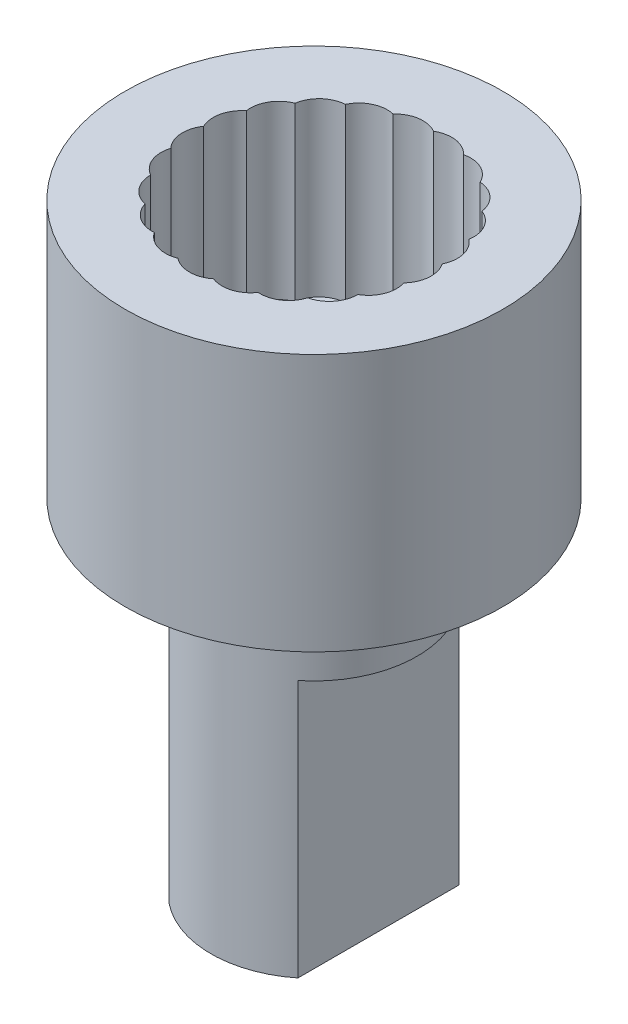
SolidWorks part; units mm, degrees
ref_plane "Front Plane" through (0, 0, 0) normal (0, 0, 1) x (1, 0, 0)
ref_plane "Top Plane" through (0, 0, 0) normal (0, 1, 0) x (1, 0, 0)
ref_plane "Right Plane" through (0, 0, 0) normal (1, 0, 0) x (0, 0, -1)
sketch "Sketch1" plane through (0, 0, 0) normal (0, 1, 0) x (1, 0, 0)
  line L0 (0, 0) -> (0, 4.4464) construction
  line L1 (0, 0) -> (0.6627, 4.3968) construction
  line L2 (0, 0) -> (1.3106, 4.2489) construction
  line L3 (0, 0) -> (1.9292, 4.0061) construction
  line L4 (0, 0) -> (2.5048, 3.6738) construction
  line L5 (0, 0) -> (3.0243, 3.2595) construction
  line L6 (0, 0) -> (3.4764, 2.7723) construction
  line L7 (0, 0) -> (3.8507, 2.2232) construction
  line L8 (0, 0) -> (4.1391, 1.6245) construction
  line L9 (0, 0) -> (4.3349, 0.9894) construction
  line L10 (0, 0) -> (4.434, 0.3323) construction
  line L11 (0, 0) -> (4.434, -0.3323) construction
  line L12 (0, 0) -> (4.3349, -0.9894) construction
  line L13 (0, 0) -> (4.1391, -1.6245) construction
  line L14 (0, 0) -> (3.8507, -2.2232) construction
  line L15 (0, 0) -> (3.4764, -2.7723) construction
  line L16 (0, 0) -> (3.0243, -3.2595) construction
  line L17 (0, 0) -> (2.5048, -3.6738) construction
  line L18 (0, 0) -> (1.9292, -4.0061) construction
  line L19 (0, 0) -> (1.3106, -4.2489) construction
  line L20 (0, 0) -> (0.6627, -4.3968) construction
  line L21 (0, 0) -> (0, -4.4464) construction
  line L22 (0, 0) -> (-0.6627, -4.3968) construction
  line L23 (0, 0) -> (-1.3106, -4.2489) construction
  line L24 (0, 0) -> (-1.9292, -4.0061) construction
  line L25 (0, 0) -> (-2.5048, -3.6738) construction
  line L26 (0, 0) -> (-3.0243, -3.2595) construction
  line L27 (0, 0) -> (-3.4764, -2.7723) construction
  line L28 (0, 0) -> (-3.8507, -2.2232) construction
  line L29 (0, 0) -> (-4.1391, -1.6245) construction
  line L30 (0, 0) -> (-4.3349, -0.9894) construction
  line L31 (0, 0) -> (-4.434, -0.3323) construction
  line L32 (0, 0) -> (-4.434, 0.3323) construction
  line L33 (0, 0) -> (-4.3349, 0.9894) construction
  line L34 (0, 0) -> (-4.1391, 1.6245) construction
  line L35 (0, 0) -> (-3.8507, 2.2232) construction
  line L36 (0, 0) -> (-3.4764, 2.7723) construction
  line L37 (0, 0) -> (-3.0243, 3.2595) construction
  line L38 (0, 0) -> (-2.5048, 3.6738) construction
  line L39 (0, 0) -> (-1.9292, 4.0061) construction
  line L40 (0, 0) -> (-1.3106, 4.2489) construction
  line L41 (0, 0) -> (-0.6627, 4.3968) construction
  circle A1 centre (0, 0) radius 2.45 construction
  circle A5 centre (0, 0) radius 3.95
  circle A14 centre (0, 0) radius 2.2653 construction
  arc A22 (-0.1666, 2.3451) -> (0, 2.2653) centre (0, 2.479) ccw
  arc A23 (-0.1666, 2.3451) -> (-0.532, 2.2901) centre (-0.3333, 2.2113) ccw
  arc A24 (-0.6677, 2.1646) -> (-0.532, 2.2901) centre (-0.7307, 2.3689) ccw
  arc A25 (0, 2.2653) -> (0.1666, 2.3451) centre (0, 2.479) ccw
  arc A26 (0.532, 2.2901) -> (0.1666, 2.3451) centre (0.3333, 2.2113) ccw
  arc A27 (0.532, 2.2901) -> (0.6677, 2.1646) centre (0.7307, 2.3689) ccw
  arc A28 (0.6677, 2.1646) -> (0.8505, 2.1918) centre (0.7307, 2.3689) ccw
  arc A29 (1.1834, 2.0315) -> (0.8505, 2.1918) centre (0.9703, 2.0148) ccw
  arc A30 (1.1834, 2.0315) -> (1.2761, 1.8716) centre (1.3965, 2.0483) ccw
  arc A31 (1.2761, 1.8716) -> (1.4588, 1.8438) centre (1.3965, 2.0483) ccw
  arc A32 (1.7296, 1.5925) -> (1.4588, 1.8438) centre (1.521, 1.6393) ccw
  arc A33 (1.7296, 1.5925) -> (1.7711, 1.4124) centre (1.9382, 1.5456) ccw
  arc A34 (1.7711, 1.4124) -> (1.9374, 1.3319) centre (1.9382, 1.5456) ccw
  arc A35 (2.1221, 1.0119) -> (1.9374, 1.3319) centre (1.9366, 1.1181) ccw
  arc A36 (2.1221, 1.0119) -> (2.1087, 0.8276) centre (2.3077, 0.9057) ccw
  arc A37 (2.1087, 0.8276) -> (2.2439, 0.7016) centre (2.3077, 0.9057) ccw
  arc A38 (2.3261, 0.3414) -> (2.2439, 0.7016) centre (2.1802, 0.4976) ccw
  arc A39 (2.3261, 0.3414) -> (2.2589, 0.1693) centre (2.4721, 0.1853) ccw
  arc A40 (2.2589, 0.1693) -> (2.351, 0.0091) centre (2.4721, 0.1853) ccw
  arc A41 (2.3234, -0.3594) -> (2.351, 0.0091) centre (2.23, -0.1671) ccw
  arc A42 (2.3234, -0.3594) -> (2.2085, -0.5041) centre (2.4169, -0.5516) ccw
  arc A43 (2.2085, -0.5041) -> (2.2493, -0.6843) centre (2.4169, -0.5516) ccw
  arc A44 (2.1143, -1.0283) -> (2.2493, -0.6843) centre (2.0817, -0.817) ccw
  arc A45 (2.1143, -1.0283) -> (1.9618, -1.1326) centre (2.1469, -1.2395) ccw
  arc A46 (1.9618, -1.1326) -> (1.9476, -1.3169) centre (2.1469, -1.2395) ccw
  arc A47 (1.7173, -1.6058) -> (1.9476, -1.3169) centre (1.7484, -1.3943) ccw
  arc A48 (1.7173, -1.6058) -> (1.5408, -1.6606) centre (1.6862, -1.8173) ccw
  arc A49 (1.5408, -1.6606) -> (1.4729, -1.8325) centre (1.6862, -1.8173) ccw
  arc A50 (1.1677, -2.0406) -> (1.4729, -1.8325) centre (1.2597, -1.8477) ccw
  arc A51 (1.1677, -2.0406) -> (0.9829, -2.0409) centre (1.0756, -2.2335) ccw
  arc A52 (0.9829, -2.0409) -> (0.8674, -2.1852) centre (1.0756, -2.2335) ccw
  arc A53 (0.5143, -2.2941) -> (0.8674, -2.1852) centre (0.6591, -2.1369) ccw
  arc A54 (0.5143, -2.2941) -> (0.3376, -2.24) centre (0.3695, -2.4513) ccw
  arc A55 (0.3376, -2.24) -> (0.1847, -2.3438) centre (0.3695, -2.4513) ccw
  arc A56 (-0.1847, -2.3438) -> (0.1847, -2.3438) centre (0, -2.2362) ccw
  arc A57 (-0.1847, -2.3438) -> (-0.3376, -2.24) centre (-0.3695, -2.4513) ccw
  arc A58 (-0.3376, -2.24) -> (-0.5143, -2.2941) centre (-0.3695, -2.4513) ccw
  arc A59 (-0.8674, -2.1852) -> (-0.5143, -2.2941) centre (-0.6591, -2.1369) ccw
  arc A60 (-0.8674, -2.1852) -> (-0.9829, -2.0409) centre (-1.0756, -2.2335) ccw
  arc A61 (-0.9829, -2.0409) -> (-1.1677, -2.0406) centre (-1.0756, -2.2335) ccw
  arc A62 (-1.4729, -1.8325) -> (-1.1677, -2.0406) centre (-1.2597, -1.8477) ccw
  arc A63 (-1.4729, -1.8325) -> (-1.5408, -1.6606) centre (-1.6862, -1.8173) ccw
  arc A64 (-1.5408, -1.6606) -> (-1.7173, -1.6058) centre (-1.6862, -1.8173) ccw
  arc A65 (-1.9476, -1.3169) -> (-1.7173, -1.6058) centre (-1.7484, -1.3943) ccw
  arc A66 (-1.9476, -1.3169) -> (-1.9618, -1.1326) centre (-2.1469, -1.2395) ccw
  arc A67 (-1.9618, -1.1326) -> (-2.1143, -1.0283) centre (-2.1469, -1.2395) ccw
  arc A68 (-2.2493, -0.6843) -> (-2.1143, -1.0283) centre (-2.0817, -0.817) ccw
  arc A69 (-2.2493, -0.6843) -> (-2.2085, -0.5041) centre (-2.4169, -0.5516) ccw
  arc A70 (-2.2085, -0.5041) -> (-2.3234, -0.3594) centre (-2.4169, -0.5516) ccw
  arc A71 (-2.351, 0.0091) -> (-2.3234, -0.3594) centre (-2.23, -0.1671) ccw
  arc A72 (-2.351, 0.0091) -> (-2.2589, 0.1693) centre (-2.4721, 0.1853) ccw
  arc A73 (-2.2589, 0.1693) -> (-2.3261, 0.3414) centre (-2.4721, 0.1853) ccw
  arc A74 (-2.2439, 0.7016) -> (-2.3261, 0.3414) centre (-2.1802, 0.4976) ccw
  arc A75 (-2.2439, 0.7016) -> (-2.1087, 0.8276) centre (-2.3077, 0.9057) ccw
  arc A76 (-2.1087, 0.8276) -> (-2.1221, 1.0119) centre (-2.3077, 0.9057) ccw
  arc A77 (-1.9374, 1.3319) -> (-2.1221, 1.0119) centre (-1.9366, 1.1181) ccw
  arc A78 (-1.9374, 1.3319) -> (-1.7711, 1.4124) centre (-1.9382, 1.5456) ccw
  arc A79 (-1.7711, 1.4124) -> (-1.7296, 1.5925) centre (-1.9382, 1.5456) ccw
  arc A80 (-1.4588, 1.8438) -> (-1.7296, 1.5925) centre (-1.521, 1.6393) ccw
  arc A81 (-1.4588, 1.8438) -> (-1.2761, 1.8716) centre (-1.3965, 2.0483) ccw
  arc A82 (-1.2761, 1.8716) -> (-1.1834, 2.0315) centre (-1.3965, 2.0483) ccw
  arc A83 (-0.8505, 2.1918) -> (-1.1834, 2.0315) centre (-0.9703, 2.0148) ccw
  arc A84 (-0.8505, 2.1918) -> (-0.6677, 2.1646) centre (-0.7307, 2.3689) ccw
  point P27 (0, 0)
  point P50 (0, 0)
  point P198 (0, 0)
  dimension "D1" = 1.5
  dimension "D2" = 4.9
  dimension "D3" = 42
  dimension "D4" = 2.2362
  dimension "D5" = 4.5305
  dimension "D6" = 4.5305
  dimension "D7" = 21
extrude "Boss-Extrude1" add sketch "Sketch1" along normal blind 4
sketch "Sketch2" plane through (0, 0, 0) normal (0, -1, 0) x (1, 0, 0)
  circle A0 centre (0, 0) radius 4.4
  dimension "D1" = 8.8
extrude "Boss-Extrude2" add sketch "Sketch2" along normal blind 2
sketch "Sketch4" plane through (0, -2, 0) normal (0, -1, 0) x (1, 0, 0)
  circle A0 centre (0, 0) radius 2.4
  dimension "D1" = 4.8
extrude "Boss-Extrude3" add sketch "Sketch4" along normal blind 2
sketch "Sketch5" plane through (0, -4, 0) normal (0, -1, 0) x (1, 0, 0)
  line L2 (-1.5, 1.8735) -> (-1.5, -1.8735)
  line L4 (1.5, 1.8735) -> (1.5, -1.8735)
  line L5 (-1.1513, 2.1058) -> (1.1513, -2.1058) construction
  line L6 (-1.1513, -2.1058) -> (1.1513, 2.1058) construction
  circle A0 centre (0, 0) radius 2.4
  point P0 (0, 0)
  circle M3 centre (0, 0) radius 2.4
extrude "Boss-Extrude4" add sketch "Sketch5" along normal blind 6 contours L4 L2 M3 region at (0, -4, 0)
sketch "Sketch6" plane through (0, 0, 0) normal (0, 1, 0) x (1, 0, 0)
  circle A0 centre (0, 0) radius 4.4
  circle A1 centre (0, 0) radius 3.95
extrude "Boss-Extrude5" add sketch "Sketch6" along normal blind 4
sketch "Sketch8" plane through (0, 4, 0) normal (0, 1, 0) x (1, 0, 0)
  line L0 (2.3886, 0.5452) -> (2.3409, 0.7542)
  line L1 (2.3886, 0.5452) -> (2.6323, 0.6008)
  arc A0 (2.3261, 0.3414) -> (2.2439, 0.7016) centre (2.1802, 0.4976) ccw construction
  arc A1 (-2.4358, 1.9425) -> (-2.9002, 1.1382) centre (-1.9366, 1.1181) ccw
  arc A2 (-2.9002, 1.1382) -> (-2.9002, 1.1382) centre (-2.9002, 1.1382) ccw
  arc A3 (-2.9002, 1.1382) -> (-3.1068, 0.2328) centre (-2.1802, 0.4976) ccw
  arc A4 (-3.1068, 0.2328) -> (-3.1068, 0.2328) centre (-3.1068, 0.2328) ccw
  arc A5 (-3.1068, 0.2328) -> (-3.0374, -0.6933) centre (-2.23, -0.1671) ccw
  arc A6 (-3.0374, -0.6933) -> (-3.0374, -0.6933) centre (-3.0374, -0.6933) ccw
  arc A7 (-3.0374, -0.6933) -> (-2.6982, -1.5578) centre (-2.0817, -0.817) ccw
  arc A8 (-2.6982, -1.5578) -> (-2.6982, -1.5578) centre (-2.6982, -1.5578) ccw
  arc A9 (-2.6982, -1.5578) -> (-2.1191, -2.2839) centre (-1.7484, -1.3943) ccw
  arc A10 (-2.1191, -2.2839) -> (-2.1191, -2.2839) centre (-2.1191, -2.2839) ccw
  arc A11 (-2.1191, -2.2839) -> (-1.3518, -2.807) centre (-1.2597, -1.8477) ccw
  arc A12 (-1.3518, -2.807) -> (-1.3518, -2.807) centre (-1.3518, -2.807) ccw
  arc A13 (-1.3518, -2.807) -> (-0.4643, -3.0808) centre (-0.6591, -2.1369) ccw
  arc A14 (-0.4643, -3.0808) -> (-0.4643, -3.0808) centre (-0.4643, -3.0808) ccw
  arc A15 (-0.4643, -3.0808) -> (0.4643, -3.0808) centre (0, -2.2362) ccw
  arc A16 (0.4643, -3.0808) -> (0.4643, -3.0808) centre (0.4643, -3.0808) ccw
  arc A17 (0.4643, -3.0808) -> (1.3518, -2.807) centre (0.6591, -2.1369) ccw
  arc A18 (1.3518, -2.807) -> (1.3518, -2.807) centre (1.3518, -2.807) ccw
  arc A19 (1.3518, -2.807) -> (2.1191, -2.2839) centre (1.2597, -1.8477) ccw
  arc A20 (2.1191, -2.2839) -> (2.1191, -2.2839) centre (2.1191, -2.2839) ccw
  arc A21 (2.1191, -2.2839) -> (2.6982, -1.5578) centre (1.7484, -1.3943) ccw
  arc A22 (2.6982, -1.5578) -> (2.6982, -1.5578) centre (2.6982, -1.5578) ccw
  arc A23 (2.6982, -1.5578) -> (3.0374, -0.6933) centre (2.0817, -0.817) ccw
  arc A24 (3.0374, -0.6933) -> (3.0374, -0.6933) centre (3.0374, -0.6933) ccw
  arc A25 (3.0374, -0.6933) -> (3.1068, 0.2328) centre (2.23, -0.1671) ccw
  arc A26 (3.1068, 0.2328) -> (3.1068, 0.2328) centre (3.1068, 0.2328) ccw
  arc A27 (3.1068, 0.2328) -> (2.9002, 1.1382) centre (2.1802, 0.4976) ccw
  arc A28 (2.9002, 1.1382) -> (2.9002, 1.1382) centre (2.9002, 1.1382) ccw
  arc A29 (2.9002, 1.1382) -> (2.4358, 1.9425) centre (1.9366, 1.1181) ccw
  arc A30 (2.4358, 1.9425) -> (2.4358, 1.9425) centre (2.4358, 1.9425) ccw
  arc A31 (2.4358, 1.9425) -> (1.7551, 2.5742) centre (1.521, 1.6393) ccw
  arc A32 (1.7551, 2.5742) -> (1.7551, 2.5742) centre (1.7551, 2.5742) ccw
  arc A33 (1.7551, 2.5742) -> (0.9183, 2.9771) centre (0.9703, 2.0148) ccw
  arc A34 (0.9183, 2.9771) -> (0.9183, 2.9771) centre (0.9183, 2.9771) ccw
  arc A35 (0.9183, 2.9771) -> (0, 3.1156) centre (0.3333, 2.2113) ccw
  arc A36 (0, 3.1156) -> (0, 3.1156) centre (0, 3.1156) ccw
  arc A37 (0, 3.1156) -> (-0.9183, 2.9771) centre (-0.3333, 2.2113) ccw
  arc A38 (-0.9183, 2.9771) -> (-0.9183, 2.9771) centre (-0.9183, 2.9771) ccw
  arc A39 (-0.9183, 2.9771) -> (-1.7551, 2.5742) centre (-0.9703, 2.0148) ccw
  arc A40 (-1.7551, 2.5742) -> (-1.7551, 2.5742) centre (-1.7551, 2.5742) ccw
  arc A41 (-1.7551, 2.5742) -> (-2.4358, 1.9425) centre (-1.521, 1.6393) ccw
  arc A42 (-2.4358, 1.9425) -> (-2.4358, 1.9425) centre (-2.4358, 1.9425) ccw
  arc A43 (0, 2.5337) -> (0, 2.5337) centre (0, 2.5337) ccw
  arc A44 (0.7468, 2.4212) -> (0, 2.5337) centre (0.3333, 2.2113) ccw
  arc A45 (0.7468, 2.4212) -> (0.7468, 2.4212) centre (0.7468, 2.4212) ccw
  arc A46 (1.4273, 2.0935) -> (0.7468, 2.4212) centre (0.9703, 2.0148) ccw
  arc A47 (1.4273, 2.0935) -> (1.4273, 2.0935) centre (1.4273, 2.0935) ccw
  arc A48 (1.981, 1.5798) -> (1.4273, 2.0935) centre (1.521, 1.6393) ccw
  arc A49 (1.981, 1.5798) -> (1.981, 1.5798) centre (1.981, 1.5798) ccw
  arc A50 (2.3586, 0.9257) -> (1.981, 1.5798) centre (1.9366, 1.1181) ccw
  arc A51 (2.3586, 0.9257) -> (2.3586, 0.9257) centre (2.3586, 0.9257) ccw
  arc A52 (2.5267, 0.1893) -> (2.3586, 0.9257) centre (2.1802, 0.4976) ccw
  arc A53 (2.5267, 0.1893) -> (2.5267, 0.1893) centre (2.5267, 0.1893) ccw
  arc A54 (2.4702, -0.5638) -> (2.5267, 0.1893) centre (2.23, -0.1671) ccw
  arc A55 (2.4702, -0.5638) -> (2.4702, -0.5638) centre (2.4702, -0.5638) ccw
  arc A56 (2.1943, -1.2669) -> (2.4702, -0.5638) centre (2.0817, -0.817) ccw
  arc A57 (2.1943, -1.2669) -> (2.1943, -1.2669) centre (2.1943, -1.2669) ccw
  arc A58 (1.7234, -1.8574) -> (2.1943, -1.2669) centre (1.7484, -1.3943) ccw
  arc A59 (1.7234, -1.8574) -> (1.7234, -1.8574) centre (1.7234, -1.8574) ccw
  arc A60 (1.0993, -2.2828) -> (1.7234, -1.8574) centre (1.2597, -1.8477) ccw
  arc A61 (1.0993, -2.2828) -> (1.0993, -2.2828) centre (1.0993, -2.2828) ccw
  arc A62 (0.3776, -2.5054) -> (1.0993, -2.2828) centre (0.6591, -2.1369) ccw
  arc A63 (0.3776, -2.5054) -> (0.3776, -2.5054) centre (0.3776, -2.5054) ccw
  arc A64 (-0.3776, -2.5054) -> (0.3776, -2.5054) centre (0, -2.2362) ccw
  arc A65 (-0.3776, -2.5054) -> (-0.3776, -2.5054) centre (-0.3776, -2.5054) ccw
  arc A66 (-1.0993, -2.2828) -> (-0.3776, -2.5054) centre (-0.6591, -2.1369) ccw
  arc A67 (-1.0993, -2.2828) -> (-1.0993, -2.2828) centre (-1.0993, -2.2828) ccw
  arc A68 (-1.7234, -1.8574) -> (-1.0993, -2.2828) centre (-1.2597, -1.8477) ccw
  arc A69 (-1.7234, -1.8574) -> (-1.7234, -1.8574) centre (-1.7234, -1.8574) ccw
  arc A70 (-2.1943, -1.2669) -> (-1.7234, -1.8574) centre (-1.7484, -1.3943) ccw
  arc A71 (-2.1943, -1.2669) -> (-2.1943, -1.2669) centre (-2.1943, -1.2669) ccw
  arc A72 (-2.4702, -0.5638) -> (-2.1943, -1.2669) centre (-2.0817, -0.817) ccw
  arc A73 (-2.4702, -0.5638) -> (-2.4702, -0.5638) centre (-2.4702, -0.5638) ccw
  arc A74 (-2.5267, 0.1893) -> (-2.4702, -0.5638) centre (-2.23, -0.1671) ccw
  arc A75 (-2.5267, 0.1893) -> (-2.5267, 0.1893) centre (-2.5267, 0.1893) ccw
  arc A76 (-2.3586, 0.9257) -> (-2.5267, 0.1893) centre (-2.1802, 0.4976) ccw
  arc A77 (-2.3586, 0.9257) -> (-2.3586, 0.9257) centre (-2.3586, 0.9257) ccw
  arc A78 (-1.981, 1.5798) -> (-2.3586, 0.9257) centre (-1.9366, 1.1181) ccw
  arc A79 (-1.981, 1.5798) -> (-1.981, 1.5798) centre (-1.981, 1.5798) ccw
  arc A80 (-1.4273, 2.0935) -> (-1.981, 1.5798) centre (-1.521, 1.6393) ccw
  arc A81 (-1.4273, 2.0935) -> (-1.4273, 2.0935) centre (-1.4273, 2.0935) ccw
  arc A82 (-0.7468, 2.4212) -> (-1.4273, 2.0935) centre (-0.9703, 2.0148) ccw
  arc A83 (-0.7468, 2.4212) -> (-0.7468, 2.4212) centre (-0.7468, 2.4212) ccw
  arc A84 (0, 2.5337) -> (-0.7468, 2.4212) centre (-0.3333, 2.2113) ccw
  arc A85 (-0.1666, 2.3451) -> (0.1666, 2.3451) centre (0, 2.479) ccw
  arc A86 (-0.1666, 2.3451) -> (-0.532, 2.2901) centre (-0.3333, 2.2113) ccw
  arc A87 (-0.8505, 2.1918) -> (-0.532, 2.2901) centre (-0.7307, 2.3689) ccw
  arc A88 (-0.8505, 2.1918) -> (-1.1834, 2.0315) centre (-0.9703, 2.0148) ccw
  arc A89 (-1.4588, 1.8438) -> (-1.1834, 2.0315) centre (-1.3965, 2.0483) ccw
  arc A90 (-1.4588, 1.8438) -> (-1.7296, 1.5925) centre (-1.521, 1.6393) ccw
  arc A91 (-1.9374, 1.3319) -> (-1.7296, 1.5925) centre (-1.9382, 1.5456) ccw
  arc A92 (-1.9374, 1.3319) -> (-2.1221, 1.0119) centre (-1.9366, 1.1181) ccw
  arc A93 (-2.2439, 0.7016) -> (-2.1221, 1.0119) centre (-2.3077, 0.9057) ccw
  arc A94 (-2.2439, 0.7016) -> (-2.3261, 0.3414) centre (-2.1802, 0.4976) ccw
  arc A95 (-2.351, 0.0091) -> (-2.3261, 0.3414) centre (-2.4721, 0.1853) ccw
  arc A96 (-2.351, 0.0091) -> (-2.3234, -0.3594) centre (-2.23, -0.1671) ccw
  arc A97 (-2.2493, -0.6843) -> (-2.3234, -0.3594) centre (-2.4169, -0.5516) ccw
  arc A98 (-2.2493, -0.6843) -> (-2.1143, -1.0283) centre (-2.0817, -0.817) ccw
  arc A99 (-1.9476, -1.3169) -> (-2.1143, -1.0283) centre (-2.1469, -1.2395) ccw
  arc A100 (-1.9476, -1.3169) -> (-1.7173, -1.6058) centre (-1.7484, -1.3943) ccw
  arc A101 (-1.4729, -1.8325) -> (-1.7173, -1.6058) centre (-1.6862, -1.8173) ccw
  arc A102 (-1.4729, -1.8325) -> (-1.1677, -2.0406) centre (-1.2597, -1.8477) ccw
  arc A103 (-0.8674, -2.1852) -> (-1.1677, -2.0406) centre (-1.0756, -2.2335) ccw
  arc A104 (-0.8674, -2.1852) -> (-0.5143, -2.2941) centre (-0.6591, -2.1369) ccw
  arc A105 (-0.1847, -2.3438) -> (-0.5143, -2.2941) centre (-0.3695, -2.4513) ccw
  arc A106 (-0.1847, -2.3438) -> (0.1847, -2.3438) centre (0, -2.2362) ccw
  arc A107 (0.5143, -2.2941) -> (0.1847, -2.3438) centre (0.3695, -2.4513) ccw
  arc A108 (0.5143, -2.2941) -> (0.8674, -2.1852) centre (0.6591, -2.1369) ccw
  arc A109 (1.1677, -2.0406) -> (0.8674, -2.1852) centre (1.0756, -2.2335) ccw
  arc A110 (1.1677, -2.0406) -> (1.4729, -1.8325) centre (1.2597, -1.8477) ccw
  arc A111 (1.7173, -1.6058) -> (1.4729, -1.8325) centre (1.6862, -1.8173) ccw
  arc A112 (1.7173, -1.6058) -> (1.9476, -1.3169) centre (1.7484, -1.3943) ccw
  arc A113 (2.1143, -1.0283) -> (1.9476, -1.3169) centre (2.1469, -1.2395) ccw
  arc A114 (2.1143, -1.0283) -> (2.2493, -0.6843) centre (2.0817, -0.817) ccw
  arc A115 (2.3234, -0.3594) -> (2.2493, -0.6843) centre (2.4169, -0.5516) ccw
  arc A116 (2.3234, -0.3594) -> (2.351, 0.0091) centre (2.23, -0.1671) ccw
  arc A117 (2.3261, 0.3414) -> (2.351, 0.0091) centre (2.4721, 0.1853) ccw
  arc A118 (2.3261, 0.3414) -> (2.2439, 0.7016) centre (2.1802, 0.4976) ccw
  arc A119 (2.1221, 1.0119) -> (2.2439, 0.7016) centre (2.3077, 0.9057) ccw
  arc A120 (2.1221, 1.0119) -> (1.9374, 1.3319) centre (1.9366, 1.1181) ccw
  arc A121 (1.7296, 1.5925) -> (1.9374, 1.3319) centre (1.9382, 1.5456) ccw
  arc A122 (1.7296, 1.5925) -> (1.4588, 1.8438) centre (1.521, 1.6393) ccw
  arc A123 (1.1834, 2.0315) -> (1.4588, 1.8438) centre (1.3965, 2.0483) ccw
  arc A124 (1.1834, 2.0315) -> (0.8505, 2.1918) centre (0.9703, 2.0148) ccw
  arc A125 (0.532, 2.2901) -> (0.8505, 2.1918) centre (0.7307, 2.3689) ccw
  arc A126 (0.532, 2.2901) -> (0.1666, 2.3451) centre (0.3333, 2.2113) ccw
  arc A127 (-0.1666, 2.3451) -> (0.1666, 2.3451) centre (0, 2.479) ccw
  arc A128 (-0.1666, 2.3451) -> (-0.532, 2.2901) centre (-0.3333, 2.2113) ccw
  arc A129 (-0.8505, 2.1918) -> (-0.532, 2.2901) centre (-0.7307, 2.3689) ccw
  arc A130 (-0.8505, 2.1918) -> (-1.1834, 2.0315) centre (-0.9703, 2.0148) ccw
  arc A131 (-1.4588, 1.8438) -> (-1.1834, 2.0315) centre (-1.3965, 2.0483) ccw
  arc A132 (-1.4588, 1.8438) -> (-1.7296, 1.5925) centre (-1.521, 1.6393) ccw
  arc A133 (-1.9374, 1.3319) -> (-1.7296, 1.5925) centre (-1.9382, 1.5456) ccw
  arc A134 (-1.9374, 1.3319) -> (-2.1221, 1.0119) centre (-1.9366, 1.1181) ccw
  arc A135 (-2.2439, 0.7016) -> (-2.1221, 1.0119) centre (-2.3077, 0.9057) ccw
  arc A136 (-2.2439, 0.7016) -> (-2.3261, 0.3414) centre (-2.1802, 0.4976) ccw
  arc A137 (-2.351, 0.0091) -> (-2.3261, 0.3414) centre (-2.4721, 0.1853) ccw
  arc A138 (-2.351, 0.0091) -> (-2.3234, -0.3594) centre (-2.23, -0.1671) ccw
  arc A139 (-2.2493, -0.6843) -> (-2.3234, -0.3594) centre (-2.4169, -0.5516) ccw
  arc A140 (-2.2493, -0.6843) -> (-2.1143, -1.0283) centre (-2.0817, -0.817) ccw
  arc A141 (-1.9476, -1.3169) -> (-2.1143, -1.0283) centre (-2.1469, -1.2395) ccw
  arc A142 (-1.9476, -1.3169) -> (-1.7173, -1.6058) centre (-1.7484, -1.3943) ccw
  arc A143 (-1.4729, -1.8325) -> (-1.7173, -1.6058) centre (-1.6862, -1.8173) ccw
  arc A144 (-1.4729, -1.8325) -> (-1.1677, -2.0406) centre (-1.2597, -1.8477) ccw
  arc A145 (-0.8674, -2.1852) -> (-1.1677, -2.0406) centre (-1.0756, -2.2335) ccw
  arc A146 (-0.8674, -2.1852) -> (-0.5143, -2.2941) centre (-0.6591, -2.1369) ccw
  arc A147 (-0.1847, -2.3438) -> (-0.5143, -2.2941) centre (-0.3695, -2.4513) ccw
  arc A148 (-0.1847, -2.3438) -> (0.1847, -2.3438) centre (0, -2.2362) ccw
  arc A149 (0.5143, -2.2941) -> (0.1847, -2.3438) centre (0.3695, -2.4513) ccw
  arc A150 (0.5143, -2.2941) -> (0.8674, -2.1852) centre (0.6591, -2.1369) ccw
  arc A151 (1.1677, -2.0406) -> (0.8674, -2.1852) centre (1.0756, -2.2335) ccw
  arc A152 (1.1677, -2.0406) -> (1.4729, -1.8325) centre (1.2597, -1.8477) ccw
  arc A153 (1.7173, -1.6058) -> (1.4729, -1.8325) centre (1.6862, -1.8173) ccw
  arc A154 (1.7173, -1.6058) -> (1.9476, -1.3169) centre (1.7484, -1.3943) ccw
  arc A155 (2.1143, -1.0283) -> (1.9476, -1.3169) centre (2.1469, -1.2395) ccw
  arc A156 (2.1143, -1.0283) -> (2.2493, -0.6843) centre (2.0817, -0.817) ccw
  arc A157 (2.3234, -0.3594) -> (2.2493, -0.6843) centre (2.4169, -0.5516) ccw
  arc A158 (2.3234, -0.3594) -> (2.351, 0.0091) centre (2.23, -0.1671) ccw
  arc A159 (2.3261, 0.3414) -> (2.351, 0.0091) centre (2.4721, 0.1853) ccw
  arc A160 (2.3261, 0.3414) -> (2.2439, 0.7016) centre (2.1802, 0.4976) ccw
  arc A161 (2.1221, 1.0119) -> (2.2439, 0.7016) centre (2.3077, 0.9057) ccw
  arc A162 (2.1221, 1.0119) -> (1.9374, 1.3319) centre (1.9366, 1.1181) ccw
  arc A163 (1.7296, 1.5925) -> (1.9374, 1.3319) centre (1.9382, 1.5456) ccw
  arc A164 (1.7296, 1.5925) -> (1.4588, 1.8438) centre (1.521, 1.6393) ccw
  arc A165 (1.1834, 2.0315) -> (1.4588, 1.8438) centre (1.3965, 2.0483) ccw
  arc A166 (1.1834, 2.0315) -> (0.8505, 2.1918) centre (0.9703, 2.0148) ccw
  arc A167 (0.532, 2.2901) -> (0.8505, 2.1918) centre (0.7307, 2.3689) ccw
  arc A168 (0.532, 2.2901) -> (0.1666, 2.3451) centre (0.3333, 2.2113) ccw
  arc A170 (-2.6459, 1.0385) -> (-2.6459, 1.0385) centre (-2.6459, 1.0385) ccw
  arc A172 (-2.8345, 0.2124) -> (-2.8345, 0.2124) centre (-2.8345, 0.2124) ccw
  arc A174 (-2.7712, -0.6325) -> (-2.7712, -0.6325) centre (-2.7712, -0.6325) ccw
  arc A176 (-2.4616, -1.4212) -> (-2.4616, -1.4212) centre (-2.4616, -1.4212) ccw
  arc A178 (-1.9333, -2.0836) -> (-1.9333, -2.0836) centre (-1.9333, -2.0836) ccw
  arc A180 (-1.2333, -2.5609) -> (-1.2333, -2.5609) centre (-1.2333, -2.5609) ccw
  arc A182 (-0.4236, -2.8107) -> (-0.4236, -2.8107) centre (-0.4236, -2.8107) ccw
  arc A184 (0.4236, -2.8107) -> (0.4236, -2.8107) centre (0.4236, -2.8107) ccw
  arc A186 (1.2333, -2.5609) -> (1.2333, -2.5609) centre (1.2333, -2.5609) ccw
  arc A188 (1.9333, -2.0836) -> (1.9333, -2.0836) centre (1.9333, -2.0836) ccw
  arc A190 (2.4616, -1.4212) -> (2.4616, -1.4212) centre (2.4616, -1.4212) ccw
  arc A192 (2.7712, -0.6325) -> (2.7712, -0.6325) centre (2.7712, -0.6325) ccw
  arc A194 (2.8345, 0.2124) -> (2.8345, 0.2124) centre (2.8345, 0.2124) ccw
  arc A196 (2.6459, 1.0385) -> (2.6459, 1.0385) centre (2.6459, 1.0385) ccw
  arc A198 (2.2223, 1.7722) -> (2.2223, 1.7722) centre (2.2223, 1.7722) ccw
  arc A200 (1.6012, 2.3485) -> (1.6012, 2.3485) centre (1.6012, 2.3485) ccw
  arc A202 (0.8378, 2.7161) -> (0.8378, 2.7161) centre (0.8378, 2.7161) ccw
  arc A204 (0, 2.8424) -> (0, 2.8424) centre (0, 2.8424) ccw
  arc A206 (-0.8378, 2.7161) -> (-0.8378, 2.7161) centre (-0.8378, 2.7161) ccw
  arc A208 (-1.6012, 2.3485) -> (-1.6012, 2.3485) centre (-1.6012, 2.3485) ccw
  arc A210 (-2.2223, 1.7722) -> (-2.2223, 1.7722) centre (-2.2223, 1.7722) ccw
  arc A211 (-2.8345, 0.2124) -> (-2.7712, -0.6325) centre (-2.23, -0.1671) ccw construction
  arc A212 (-2.6459, 1.0385) -> (-2.8345, 0.2124) centre (-2.1802, 0.4976) ccw construction
  arc A213 (-2.2223, 1.7722) -> (-2.6459, 1.0385) centre (-1.9366, 1.1181) ccw construction
  arc A214 (-1.6012, 2.3485) -> (-2.2223, 1.7722) centre (-1.521, 1.6393) ccw construction
  arc A215 (-0.8378, 2.7161) -> (-1.6012, 2.3485) centre (-0.9703, 2.0148) ccw construction
  arc A216 (0.8378, 2.7161) -> (0, 2.8424) centre (0.3333, 2.2113) ccw construction
  arc A217 (0, 2.8424) -> (-0.8378, 2.7161) centre (-0.3333, 2.2113) ccw construction
  arc A218 (1.6012, 2.3485) -> (0.8378, 2.7161) centre (0.9703, 2.0148) ccw construction
  arc A219 (2.2223, 1.7722) -> (1.6012, 2.3485) centre (1.521, 1.6393) ccw construction
  arc A220 (2.6459, 1.0385) -> (2.2223, 1.7722) centre (1.9366, 1.1181) ccw construction
  arc A221 (2.8345, 0.2124) -> (2.6459, 1.0385) centre (2.1802, 0.4976) ccw construction
  arc A222 (2.7712, -0.6325) -> (2.8345, 0.2124) centre (2.23, -0.1671) ccw construction
  arc A223 (2.4616, -1.4212) -> (2.7712, -0.6325) centre (2.0817, -0.817) ccw construction
  arc A224 (1.9333, -2.0836) -> (2.4616, -1.4212) centre (1.7484, -1.3943) ccw construction
  arc A225 (1.2333, -2.5609) -> (1.9333, -2.0836) centre (1.2597, -1.8477) ccw construction
  arc A226 (0.4236, -2.8107) -> (1.2333, -2.5609) centre (0.6591, -2.1369) ccw construction
  arc A227 (-0.4236, -2.8107) -> (0.4236, -2.8107) centre (0, -2.2362) ccw construction
  arc A228 (-1.2333, -2.5609) -> (-0.4236, -2.8107) centre (-0.6591, -2.1369) ccw construction
  arc A229 (-1.9333, -2.0836) -> (-1.2333, -2.5609) centre (-1.2597, -1.8477) ccw construction
  arc A230 (-2.4616, -1.4212) -> (-1.9333, -2.0836) centre (-1.7484, -1.3943) ccw construction
  arc A231 (-2.7712, -0.6325) -> (-2.4616, -1.4212) centre (-2.0817, -0.817) ccw construction
  arc M54 (2.2439, 0.7016) -> (2.3261, 0.3414) centre (2.1802, 0.4976) cw
  arc M55 (2.3261, 0.3414) -> (2.351, 0.0091) centre (2.4721, 0.1853) ccw
  arc M56 (2.351, 0.0091) -> (2.3234, -0.3594) centre (2.23, -0.1671) cw
  arc M57 (2.3234, -0.3594) -> (2.2493, -0.6843) centre (2.4169, -0.5516) ccw
  arc M58 (2.2493, -0.6843) -> (2.1143, -1.0283) centre (2.0817, -0.817) cw
  arc M59 (2.1143, -1.0283) -> (1.9476, -1.3169) centre (2.1469, -1.2395) ccw
  arc M60 (1.9476, -1.3169) -> (1.7173, -1.6058) centre (1.7484, -1.3943) cw
  arc M61 (1.7173, -1.6058) -> (1.4729, -1.8325) centre (1.6862, -1.8173) ccw
  arc M62 (1.4729, -1.8325) -> (1.1677, -2.0406) centre (1.2597, -1.8477) cw
  arc M63 (1.1677, -2.0406) -> (0.8674, -2.1852) centre (1.0756, -2.2335) ccw
  arc M64 (0.8674, -2.1852) -> (0.5143, -2.2941) centre (0.6591, -2.1369) cw
  arc M65 (0.5143, -2.2941) -> (0.1847, -2.3438) centre (0.3695, -2.4513) ccw
  arc M66 (0.1847, -2.3438) -> (-0.1847, -2.3438) centre (0, -2.2362) cw
  arc M67 (-0.1847, -2.3438) -> (-0.5143, -2.2941) centre (-0.3695, -2.4513) ccw
  arc M68 (-0.5143, -2.2941) -> (-0.8674, -2.1852) centre (-0.6591, -2.1369) cw
  arc M69 (-0.8674, -2.1852) -> (-1.1677, -2.0406) centre (-1.0756, -2.2335) ccw
  arc M70 (-1.1677, -2.0406) -> (-1.4729, -1.8325) centre (-1.2597, -1.8477) cw
  arc M71 (-1.4729, -1.8325) -> (-1.7173, -1.6058) centre (-1.6862, -1.8173) ccw
  arc M72 (-1.7173, -1.6058) -> (-1.9476, -1.3169) centre (-1.7484, -1.3943) cw
  arc M73 (-1.9476, -1.3169) -> (-2.1143, -1.0283) centre (-2.1469, -1.2395) ccw
  arc M74 (-2.1143, -1.0283) -> (-2.2493, -0.6843) centre (-2.0817, -0.817) cw
  arc M75 (-2.2493, -0.6843) -> (-2.3234, -0.3594) centre (-2.4169, -0.5516) ccw
  arc M76 (-2.3234, -0.3594) -> (-2.351, 0.0091) centre (-2.23, -0.1671) cw
  arc M77 (-2.351, 0.0091) -> (-2.3261, 0.3414) centre (-2.4721, 0.1853) ccw
  arc M78 (-2.3261, 0.3414) -> (-2.2439, 0.7016) centre (-2.1802, 0.4976) cw
  arc M79 (-2.2439, 0.7016) -> (-2.1221, 1.0119) centre (-2.3077, 0.9057) ccw
  arc M80 (-2.1221, 1.0119) -> (-1.9374, 1.3319) centre (-1.9366, 1.1181) cw
  arc M81 (-1.9374, 1.3319) -> (-1.7296, 1.5925) centre (-1.9382, 1.5456) ccw
  arc M82 (-1.7296, 1.5925) -> (-1.4588, 1.8438) centre (-1.521, 1.6393) cw
  arc M83 (-1.4588, 1.8438) -> (-1.1834, 2.0315) centre (-1.3965, 2.0483) ccw
  arc M84 (-1.1834, 2.0315) -> (-0.8505, 2.1918) centre (-0.9703, 2.0148) cw
  arc M85 (-0.8505, 2.1918) -> (-0.532, 2.2901) centre (-0.7307, 2.3689) ccw
  dimension "D1" = 0
  dimension "D2" = 0.25
  dimension "D3" = 0.5
extrude "Cut-Extrude1" cut sketch "Sketch8" against normal blind 4 contours A44 A84 A82 A80 A78 A76 A74 A72 A70 A68 A66 A64 A62 A60 A58 A56 A54 A52 M54 M55 M56 M57 M58 M59 M60 M61 M62 M63 M64 M65 M66 M67 M68 M69 M70 M71 M72 M73 M74 M75 M76 M77 M78 M79 M80 M81 M82 M83 M84 M85 region at (2.5556, 4, -0.4012)
extrude "Cut-Extrude2" cut sketch "Sketch8<3>" against normal blind 4 contours A39 A41 A1 A3 A5 A7 A9 A11 A13 A15 A17 A19 A21 A23 A25 A27 A29 A31 A33 A35 A37 A84 A44 A46 A48 A50 A52 A54 A56 A58 A60 A62 A64 A66 A68 A70 A72 A74 A76 A78 A80 A82 region at (-2.1152, 4, -2.2796)
sketch "Sketch8<3>" plane through (0, 4, 0) normal (0, 1, 0) x (1, 0, 0) same geometry as "Sketch8"
sketch "Sketch9" plane through (0, 4, 0) normal (0, 1, 0) x (1, 0, 0)
  arc A0 (-0.821, 2.6615) -> (-1.569, 2.3013) centre (-0.9703, 2.0148) ccw
  arc A1 (-1.569, 2.3013) -> (-2.1776, 1.7366) centre (-1.521, 1.6393) ccw
  arc A2 (-2.1776, 1.7366) -> (-2.5927, 1.0176) centre (-1.9366, 1.1181) ccw
  arc A3 (-2.5927, 1.0176) -> (-2.7775, 0.2081) centre (-2.1802, 0.4976) ccw
  arc A4 (-2.7775, 0.2081) -> (-2.7154, -0.6198) centre (-2.23, -0.1671) ccw
  arc A5 (-2.7154, -0.6198) -> (-2.4121, -1.3926) centre (-2.0817, -0.817) ccw
  arc A6 (-2.4121, -1.3926) -> (-1.8945, -2.0418) centre (-1.7484, -1.3943) ccw
  arc A7 (-1.8945, -2.0418) -> (-1.2085, -2.5094) centre (-1.2597, -1.8477) ccw
  arc A8 (-1.2085, -2.5094) -> (-0.4151, -2.7542) centre (-0.6591, -2.1369) ccw
  arc A9 (-0.4151, -2.7542) -> (0.4151, -2.7542) centre (0, -2.2362) ccw
  arc A10 (0.4151, -2.7542) -> (1.2085, -2.5094) centre (0.6591, -2.1369) ccw
  arc A11 (1.2085, -2.5094) -> (1.8945, -2.0418) centre (1.2597, -1.8477) ccw
  arc A12 (1.8945, -2.0418) -> (2.4121, -1.3926) centre (1.7484, -1.3943) ccw
  arc A13 (2.4121, -1.3926) -> (2.7154, -0.6198) centre (2.0817, -0.817) ccw
  arc A14 (2.7154, -0.6198) -> (2.7775, 0.2081) centre (2.23, -0.1671) ccw
  arc A15 (2.7775, 0.2081) -> (2.5927, 1.0176) centre (2.1802, 0.4976) ccw
  arc A16 (2.5927, 1.0176) -> (2.1776, 1.7366) centre (1.9366, 1.1181) ccw
  arc A17 (2.1776, 1.7366) -> (1.569, 2.3013) centre (1.521, 1.6393) ccw
  arc A18 (1.569, 2.3013) -> (0.821, 2.6615) centre (0.9703, 2.0148) ccw
  arc A19 (0.821, 2.6615) -> (0, 2.7853) centre (0.3333, 2.2113) ccw
  arc A20 (0, 2.7853) -> (-0.821, 2.6615) centre (-0.3333, 2.2113) ccw
  arc A42 (-0.9183, 2.9771) -> (-1.7551, 2.5742) centre (-0.9703, 2.0148) ccw
  arc A43 (-1.7551, 2.5742) -> (-2.4358, 1.9425) centre (-1.521, 1.6393) ccw
  arc A44 (-2.4358, 1.9425) -> (-2.9002, 1.1382) centre (-1.9366, 1.1181) ccw
  arc A45 (-2.9002, 1.1382) -> (-3.1068, 0.2328) centre (-2.1802, 0.4976) ccw
  arc A46 (-3.1068, 0.2328) -> (-3.0374, -0.6933) centre (-2.23, -0.1671) ccw
  arc A47 (-3.0374, -0.6933) -> (-2.6982, -1.5578) centre (-2.0817, -0.817) ccw
  arc A48 (-2.6982, -1.5578) -> (-2.1191, -2.2839) centre (-1.7484, -1.3943) ccw
  arc A49 (-2.1191, -2.2839) -> (-1.3518, -2.807) centre (-1.2597, -1.8477) ccw
  arc A50 (-1.3518, -2.807) -> (-0.4643, -3.0808) centre (-0.6591, -2.1369) ccw
  arc A51 (-0.4643, -3.0808) -> (0.4643, -3.0808) centre (0, -2.2362) ccw
  arc A52 (0.4643, -3.0808) -> (1.3518, -2.807) centre (0.6591, -2.1369) ccw
  arc A53 (1.3518, -2.807) -> (2.1191, -2.2839) centre (1.2597, -1.8477) ccw
  arc A54 (2.1191, -2.2839) -> (2.6982, -1.5578) centre (1.7484, -1.3943) ccw
  arc A55 (2.6982, -1.5578) -> (3.0374, -0.6933) centre (2.0817, -0.817) ccw
  arc A56 (3.0374, -0.6933) -> (3.1068, 0.2328) centre (2.23, -0.1671) ccw
  arc A57 (3.1068, 0.2328) -> (2.9002, 1.1382) centre (2.1802, 0.4976) ccw
  arc A58 (2.9002, 1.1382) -> (2.4358, 1.9425) centre (1.9366, 1.1181) ccw
  arc A59 (2.4358, 1.9425) -> (1.7551, 2.5742) centre (1.521, 1.6393) ccw
  arc A60 (1.7551, 2.5742) -> (0.9183, 2.9771) centre (0.9703, 2.0148) ccw
  arc A61 (0.9183, 2.9771) -> (0, 3.1156) centre (0.3333, 2.2113) ccw
  arc A62 (0, 3.1156) -> (-0.9183, 2.9771) centre (-0.3333, 2.2113) ccw
  arc A63 (-0.9183, 2.9771) -> (-1.7551, 2.5742) centre (-0.9703, 2.0148) ccw
  arc A64 (-1.7551, 2.5742) -> (-2.4358, 1.9425) centre (-1.521, 1.6393) ccw
  arc A65 (-2.4358, 1.9425) -> (-2.9002, 1.1382) centre (-1.9366, 1.1181) ccw
  arc A66 (-2.9002, 1.1382) -> (-3.1068, 0.2328) centre (-2.1802, 0.4976) ccw
  arc A67 (-3.1068, 0.2328) -> (-3.0374, -0.6933) centre (-2.23, -0.1671) ccw
  arc A68 (-3.0374, -0.6933) -> (-2.6982, -1.5578) centre (-2.0817, -0.817) ccw
  arc A69 (-2.6982, -1.5578) -> (-2.1191, -2.2839) centre (-1.7484, -1.3943) ccw
  arc A70 (-2.1191, -2.2839) -> (-1.3518, -2.807) centre (-1.2597, -1.8477) ccw
  arc A71 (-1.3518, -2.807) -> (-0.4643, -3.0808) centre (-0.6591, -2.1369) ccw
  arc A72 (-0.4643, -3.0808) -> (0.4643, -3.0808) centre (0, -2.2362) ccw
  arc A73 (0.4643, -3.0808) -> (1.3518, -2.807) centre (0.6591, -2.1369) ccw
  arc A74 (1.3518, -2.807) -> (2.1191, -2.2839) centre (1.2597, -1.8477) ccw
  arc A75 (2.1191, -2.2839) -> (2.6982, -1.5578) centre (1.7484, -1.3943) ccw
  arc A76 (2.6982, -1.5578) -> (3.0374, -0.6933) centre (2.0817, -0.817) ccw
  arc A77 (3.0374, -0.6933) -> (3.1068, 0.2328) centre (2.23, -0.1671) ccw
  arc A78 (3.1068, 0.2328) -> (2.9002, 1.1382) centre (2.1802, 0.4976) ccw
  arc A79 (2.9002, 1.1382) -> (2.4358, 1.9425) centre (1.9366, 1.1181) ccw
  arc A80 (2.4358, 1.9425) -> (1.7551, 2.5742) centre (1.521, 1.6393) ccw
  arc A81 (1.7551, 2.5742) -> (0.9183, 2.9771) centre (0.9703, 2.0148) ccw
  arc A82 (0.9183, 2.9771) -> (0, 3.1156) centre (0.3333, 2.2113) ccw
  arc A83 (0, 3.1156) -> (-0.9183, 2.9771) centre (-0.3333, 2.2113) ccw
  dimension "D1" = 0
  dimension "D2" = 0.3
extrude "Boss-Extrude6" add sketch "Sketch9" against normal blind 4
equation "\"r0.247\"=0.713093"
